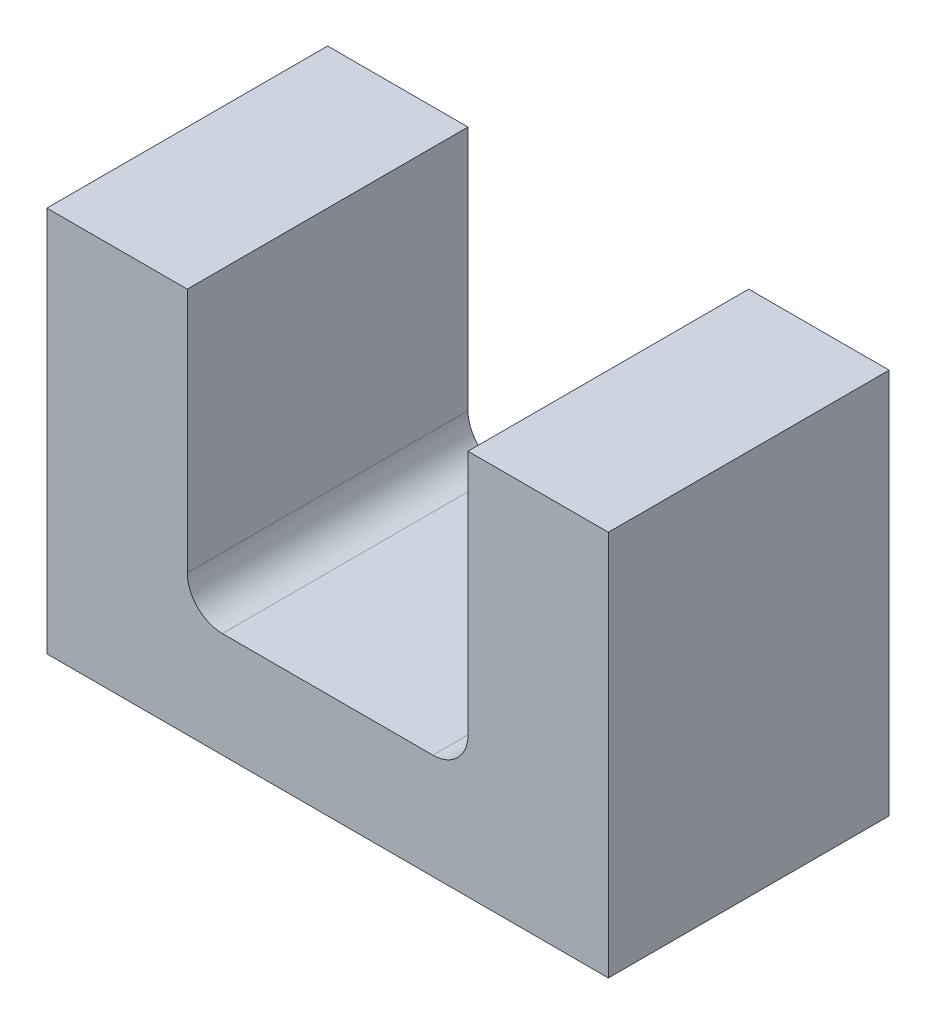
SolidWorks part; units mm, degrees
ref_plane "前视基准面" through (0, 0, 0) normal (0, 0, 1) x (1, 0, 0)
ref_plane "上视基准面" through (0, 0, 0) normal (0, 1, 0) x (1, 0, 0)
ref_plane "右视基准面" through (0, 0, 0) normal (1, 0, 0) x (0, 0, -1)
sketch "草图1" plane through (0, 0, 0) normal (0, 1, 0) x (1, 0, 0)
  line L0 (-2, 2) -> (-2, -2)
  line L1 (-4, 2) -> (4, 2)
  line L2 (-4, 2) -> (-4, -2)
  line L3 (-4, -2) -> (4, -2)
  line L4 (4, 2) -> (4, -2)
  line L5 (0, -2) -> (0, 2) construction
  line L6 (-4, 0) -> (4, 0) construction
  line L7 (2, 2) -> (2, -2)
  point P0 (0, 0)
  dimension "D1" = 8
  dimension "D2" = 4
  dimension "D3" = 2
  dimension "D4" = 2
extrude "凸台-拉伸1" add sketch "草图1" along normal blind 5.5 contours L2 L3 L0 L1 | L1 L7 L3 L4 region at (-3, 0, 0) region at (3, 0, 0)
extrude "凸台-拉伸2" add sketch "草图1<3>" along normal blind 1.5 contours L7 L1 L0 L3 region at (0, 0, 0)
sketch "草图1<3>" plane through (0, 0, 0) normal (0, 1, 0) x (1, 0, 0) same geometry as "草图1"
fillet "圆角1" radius 0.5 2 edges at (2, 1.5, 0) (-2, 1.5, 0)
